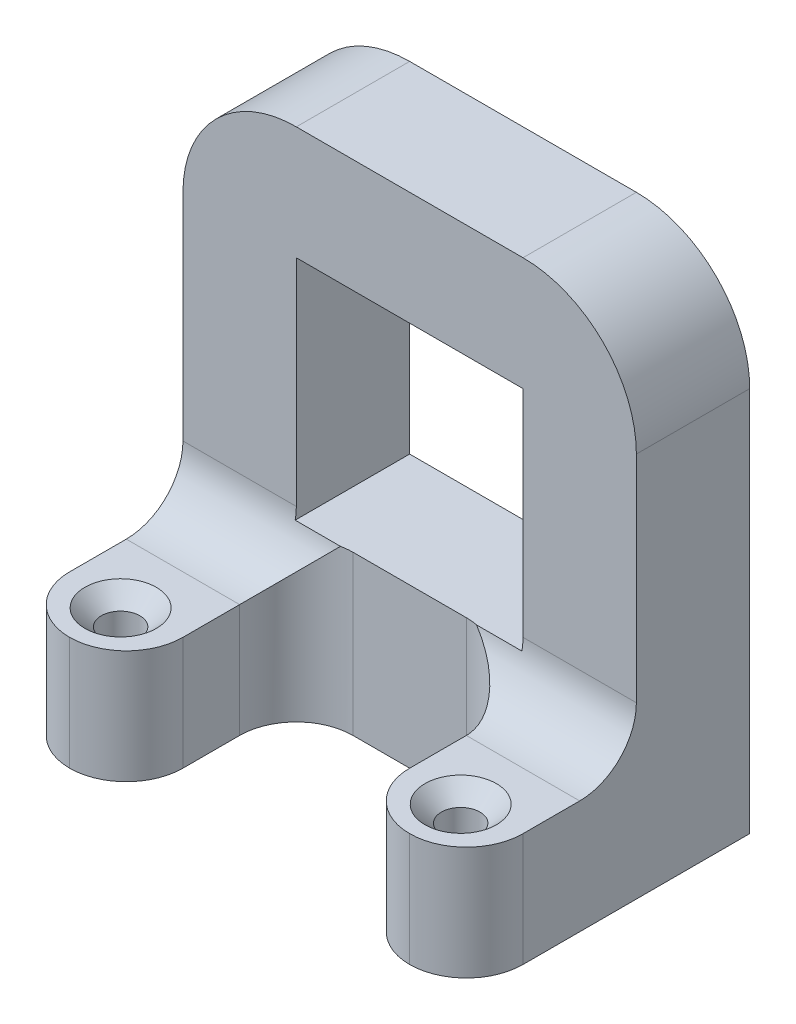
SolidWorks part; units mm, degrees
ref_plane "Plan de face" through (0, 0, 0) normal (0, 0, 1) x (1, 0, 0)
ref_plane "Plan de dessus" through (0, 0, 0) normal (0, 1, 0) x (1, 0, 0)
ref_plane "Plan de droite" through (0, 0, 0) normal (1, 0, 0) x (0, 0, -1)
sketch "Esquisse1" plane through (0, 0, 0) normal (0, 0, 1) x (1, 0, 0)
  line L0 (0, 0) -> (40, 0)
  line L1 (0, 0) -> (40, 0) construction
  line L2 (0, 0) -> (0, 44) construction
  line L3 (0, 44) -> (40, 44) construction
  line L4 (40, 0) -> (40, 44) construction
  line L5 (40, 0) -> (40, 44)
  line L6 (40, 44) -> (0, 44)
  line L7 (0, 44) -> (0, 0)
  line L9 (10, 34) -> (30, 34)
  line L10 (10, 34) -> (10, 14)
  line L11 (10, 14) -> (30, 14)
  line L12 (30, 34) -> (30, 14)
  dimension "D1" = 40
  dimension "D2" = 44
  dimension "D3" = 10
  dimension "D4" = 10
  dimension "D5" = 10
  dimension "D6" = 14
extrude "Boss.-Extru.1" add sketch "Esquisse1" along normal blind 10
sketch "Esquisse3" plane through (0, 0, 10) normal (0, 0, 1) x (1, 0, 0)
  line L0 (30, 0) -> (40, 0)
  line L3 (0, 10) -> (10, 10)
  line L4 (0, 44) -> (0, 0)
  line L5 (0, 0) -> (40, 0)
  line L6 (40, 0) -> (40, 44)
  line L7 (40, 44) -> (0, 44)
  line L8 (0, 10) -> (0, 0)
  line L9 (0, 0) -> (10, 0)
  line L12 (10, 0) -> (10, 10)
  line L14 (40, 0) -> (40, 10)
  line L15 (40, 10) -> (30, 10)
  line L16 (30, 0) -> (30, 10)
  line L17 (0, 0) -> (40, 0) construction
  dimension "D3" = 10
  dimension "D4" = 10
  dimension "D5" = 10
  dimension "D2" = 10
extrude "Boss.-Extru.2" add sketch "Esquisse3" along normal blind 15
sketch "Esquisse4" plane through (0, 10, 0) normal (0, 1, 0) x (1, 0, 0)
  line L0 (0, -25) -> (0, -10) construction
  line L2 (40, -25) -> (40, -10) construction
  line L4 (40, -25) -> (30, -25) construction
  line L5 (10, -25) -> (0, -25) construction
  circle A0 centre (5, -20.5) radius 1.5
  circle A1 centre (35, -20.5) radius 1.5
  dimension "D3" = 3
  dimension "D4" = 3
  dimension "D1" = 5
  dimension "D5" = 5
  dimension "D2" = 4.5
  dimension "D6" = 4.5
hole_wizard "Fraisage pour vis à tête fraisée M31" positions "Esquisse5" profile "Esquisse6" countersink size "M3" standard "ISO" end condition through all
sketch "Esquisse5" plane through (0, 10, 0) normal (0, 1, 0) x (1, 0, 0)
  point P0 (5, -20.5)
  point P3 (35, -20.5)
sketch "Esquisse6" plane through (5, 10, 20.5) normal (1, 0, 0) x (0, 0, 1)
  line L0 (0, 0) -> (0, 10)
  line L1 (0, 10) -> (1.7, 10)
  line L2 (1.7, 10) -> (1.7, 1.45)
  line L3 (1.7, 1.45) -> (3.15, 0)
  line L5 (3.15, 0) -> (0, 0)
  line L6 (-1.7, 1.45) -> (-3.15, 0) construction
  line L11 (0, -6.35) -> (0, 107.95) construction
  dimension "Diamètre du perçage jusqu'au prochain" = 3.4
  dimension "Profondeur du perçage jusqu'au prochain" = 10
  dimension "Diamètre du fraisage entrant" = 6.3
  dimension "Angle du fraisage entrant" = 90
ref_plane "Plan1" through (0, 0, 5) normal (0, 0, 1) x (1, 0, 0)
fillet "Congé2" radius 10 2 edges at (0, 44, 5) (40, 44, 5)
fillet "Congé3" radius 5 8 edges at (35, 10, 10) (5, 10, 10) (30, 5, 10) (10, 5, 10) (40, 5, 25) (30, 5, 25) (10, 5, 25) (0, 5, 25)
equation "\"largeur_cremail\"= 20"
equation "\"hauteur_cremail\"= 20"
equation "\"epaiss_cadre\"= 10"
equation "\"hauteur_basecremail_sol\"= 4"
equation "\"D1@Esquisse1\"=\"largeur_cremail\"+\"epaiss_cadre\"*2"
equation "\"D2@Esquisse1\"=\"hauteur_basecremail_sol\"+\"hauteur_cremail\"+\"epaiss_cadre\"*2"
equation "\"D3@Esquisse1\"=\"epaiss_cadre\""
equation "\"D4@Esquisse1\"=\"epaiss_cadre\""
equation "\"D5@Esquisse1\"=\"epaiss_cadre\""
equation "\"D6@Esquisse1\"=\"hauteur_basecremail_sol\"+\"epaiss_cadre\""
equation "\"D1@Boss.-Extru.1\"=\"epaiss_cadre\""
equation "\"D2@Esquisse3\"=\"epaiss_cadre\""
equation "\"D4@Esquisse3\"=\"epaiss_cadre\""
equation "\"D5@Esquisse3\"=\"D3@Esquisse3\""
equation "\"D1@Esquisse4\"=\"epaiss_cadre\"/2"
equation "\"D5@Esquisse4\"=\"epaiss_cadre\"/2"
